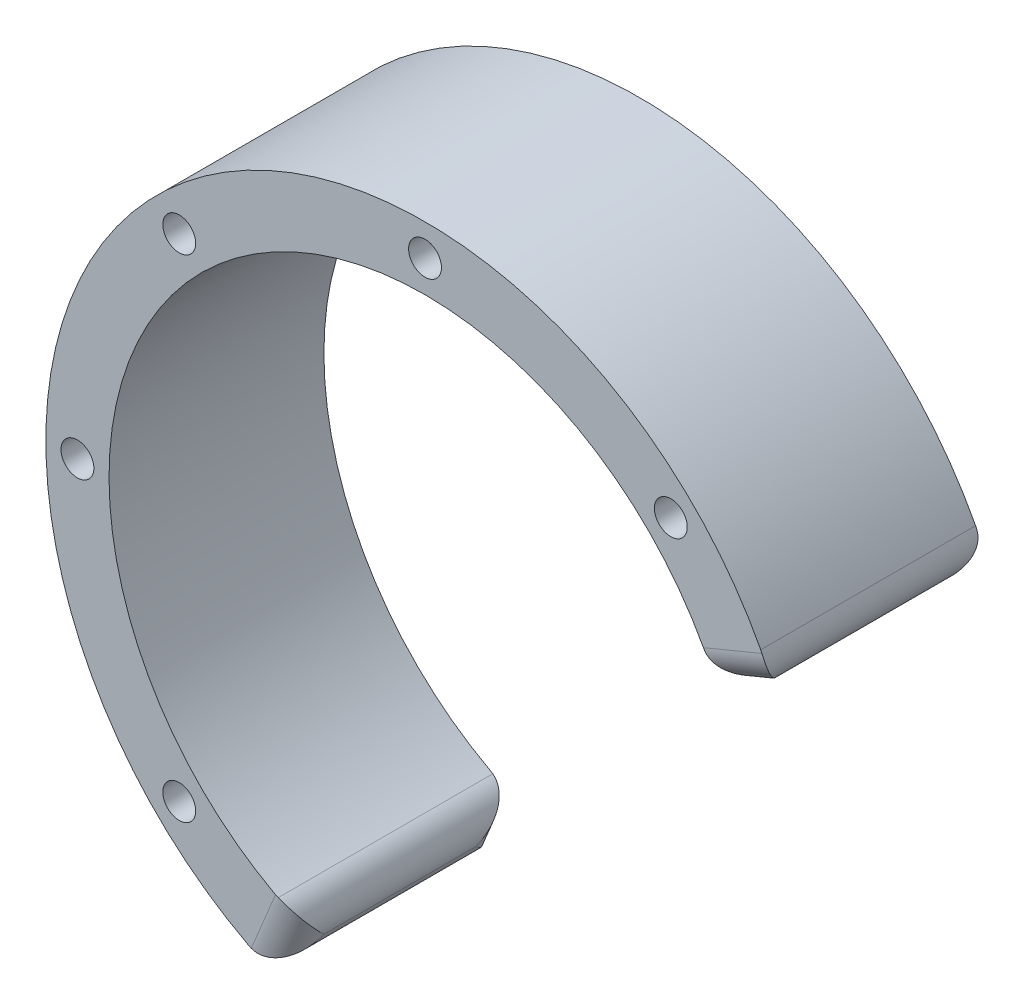
SolidWorks part; units mm, degrees
ref_plane "前视基准面" through (0, 0, 0) normal (0, 0, 1) x (1, 0, 0)
ref_plane "上视基准面" through (0, 0, 0) normal (0, 1, 0) x (1, 0, 0)
ref_plane "右视基准面" through (0, 0, 0) normal (1, 0, 0) x (0, 0, -1)
other "Configuration Table"
sketch "草图2" plane through (0, 0, 0) normal (0, 0, 1) x (1, 0, 0)
  circle A0 centre (0, 0) radius 55 construction
  circle A1 centre (0, 55) radius 2.6
  circle A2 centre (38.8909, 38.8909) radius 2.6
  circle A3 centre (55, 0) radius 2.6
  circle A4 centre (38.8909, -38.8909) radius 2.6
  circle A5 centre (0, -55) radius 2.6
  circle A6 centre (-38.8909, -38.8909) radius 2.6
  circle A7 centre (-55, 0) radius 2.6
  circle A8 centre (-38.8909, 38.8909) radius 2.6
  circle A9 centre (0, 0) radius 50
  circle A10 centre (0, 0) radius 60
  point P21 (0, 0)
  dimension "D1" = 110
  dimension "D2" = 5.2
  dimension "D4" = 100
  dimension "D5" = 120
  dimension "D3" = 8
extrude "凸台-拉伸1" add sketch "草图2" along normal blind 34
sketch "草图3" plane through (0, 0, 34) normal (0, 0, 1) x (1, 0, 0)
  line L0 (0, 0) -> (0, 64.8134) construction
  line L1 (0, 0) -> (28.6469, 69.1598) construction
  line L2 (0, 0) -> (55.4328, 22.961)
  line L3 (0, 0) -> (-22.961, -55.4328)
  circle A0 centre (0, 0) radius 50 construction
  circle A1 centre (0, 0) radius 60
  circle A2 centre (0, 0) radius 60
  circle A3 centre (0, 0) radius 50
  circle A4 centre (0, 0) radius 60 construction
  circle M8 centre (38.8909, -38.8909) radius 2.6
  circle M10 centre (0, 0) radius 60
  circle M12 centre (55, 0) radius 2.6
  circle M13 centre (0, -55) radius 2.6
  circle M15 centre (0, 0) radius 50
  dimension "D1" = 22.5
  dimension "D2" = 45
  dimension "D3" = 0
extrude "切除-拉伸1" cut sketch "草图3" against normal blind 34 contours L3 L2 M15 M10 M8 M12 M13 region at (51.2624, 19.9637, 34)
fillet "圆角1" radius 5 8 edges at (55.4328, 22.961, 17) (50.8134, 21.0476, 0) (46.194, 19.1342, 17) (50.8134, 21.0476, 34) (-19.1342, -46.194, 17) (-21.0476, -50.8134, 0) (-22.961, -55.4328, 17) (-21.0476, -50.8134, 34)
